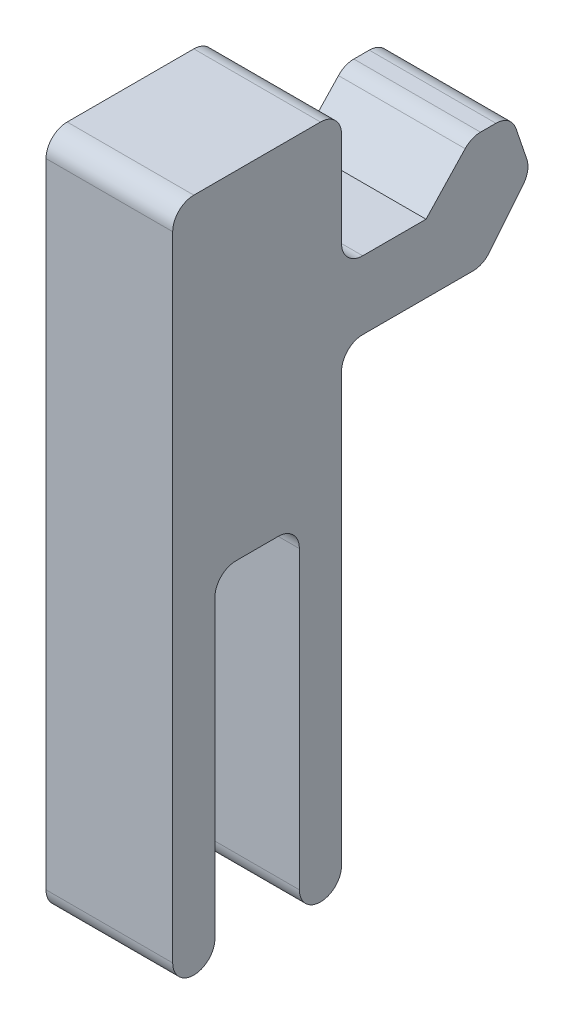
SolidWorks part; units mm, degrees
ref_plane "Alzado" through (0, 0, 0) normal (0, 0, 1) x (1, 0, 0)
ref_plane "Planta" through (0, 0, 0) normal (0, 1, 0) x (1, 0, 0)
ref_plane "Vista lateral" through (0, 0, 0) normal (1, 0, 0) x (0, 0, -1)
sketch "Croquis1" plane through (0, 0, 0) normal (1, 0, 0) x (0, 0, -1)
  line L1 (-2, 8) -> (2, 8)
  line L2 (-2, 8) -> (-2, -8)
  line L3 (-2, -8) -> (2, -8)
  line L16 (2, 8) -> (2, -8)
  dimension "D1" = 2
  dimension "D2" = 8
  dimension "D3" = 16
  dimension "D4" = 4
extrude "Saliente-Extruir1" add sketch "Croquis1" along normal blind 3
sketch "Croquis2" plane through (3, 0, 0) normal (1, 0, 0) x (0, 0, -1)
  line L0 (0, 0) -> (0, -9.3656) construction
  line L1 (-2, -8) -> (2, -8) construction
  line L2 (-1, -8) -> (1, -8)
  line L3 (-1, -8) -> (-1, 0)
  line L4 (-1, 0) -> (1, 0)
  line L5 (1, -8) -> (1, 0)
  dimension "D1" = 1
  dimension "D2" = 1
  dimension "D3" = 8
extrude "Cortar-Extruir1" cut sketch "Croquis2" against normal up to surface (3 mm away) up to face at (0, 0, 0)
sketch "Croquis4" plane through (3, 0, 0) normal (1, 0, 0) x (0, 0, -1)
  line L0 (2, 4.7559) -> (4, 4.7559)
  line L2 (2, -8) -> (2, 8) construction
  line L9 (1, 0) -> (-1, 0) construction
  line L10 (0, 0) -> (0, 10.8389) construction
  line L11 (4, 4.7559) -> (5.0744, 5.8963)
  line L12 (5.0744, 5.8963) -> (6.0144, 5.8963)
  line L13 (6.0144, 5.8963) -> (6.4764, 4.5311)
  line L14 (6.4764, 4.5311) -> (5.3503, 3.1377)
  line L15 (5.3503, 3.1377) -> (2, 3.1377)
  line L16 (2, 4.7559) -> (2, 3.1377)
  point P8 (5.0744, 5.8963)
  point P9 (5.3503, 3.1377)
  point P15 (6.4764, 4.5311)
  point P16 (6.0144, 5.8963)
  dimension "D1" = 3.1377
  dimension "D2" = 4.7559
  dimension "D3" = 5.8963
  dimension "D4" = 2
extrude "Saliente-Extruir2" add sketch "Croquis4" against normal up to surface (3 mm away) up to face at (0, -2, 0)
fillet "Redondeo2" radius 0.5 14 edges at (1.5, 5.8963, -5.0744) (1.5, 5.8963, -6.0144) (1.5, 4.5311, -6.4764) (1.5, 3.1377, -2) (1.5, 3.1377, -5.3503) (1.5, 4.7559, -2) (1.5, 8, -2) (1.5, 8, 2) (1.5, 0, 1) (1.5, 0, -1) (1.5, -8, 2) (1.5, -8, -1) (1.5, -8, -2) (1.5, -8, 1)
